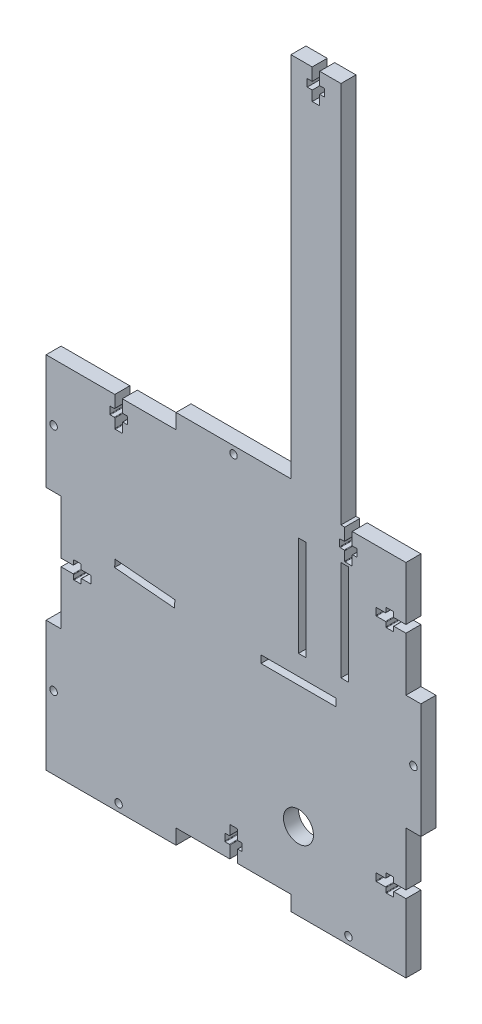
SolidWorks part; units mm, degrees
ref_plane "Front Plane" through (0, 0, 0) normal (0, 0, 1) x (1, 0, 0)
ref_plane "Top Plane" through (0, 0, 0) normal (0, 1, 0) x (1, 0, 0)
ref_plane "Right Plane" through (0, 0, 0) normal (1, 0, 0) x (0, 0, -1)
sketch "Sketch1" plane through (0, 0, 0) normal (0, 0, 1) x (1, 0, 0)
  line L0 (-69, 69) -> (-23, 69)
  line L5 (-75, -75) -> (75, -75) construction
  line L6 (-75, -75) -> (-75, 75) construction
  line L7 (-75, 75) -> (75, 75) construction
  line L8 (75, -75) -> (75, 75) construction
  line L9 (75, 23) -> (69, 23)
  line L10 (69, -23) -> (75, -23)
  line L11 (-69, -69) -> (69, -69) construction
  line L12 (-69, -69) -> (-69, 69) construction
  line L13 (-69, 69) -> (69, 69) construction
  line L14 (69, -69) -> (69, 69) construction
  line L15 (-69, -69) -> (69, 69) construction
  line L16 (69, -69) -> (69, -23)
  line L17 (-23, 69) -> (-23, 75)
  line L18 (-23, 75) -> (23, 75)
  line L19 (23, 75) -> (23, 69)
  line L20 (23, 69) -> (69, 69)
  line L21 (75, -23) -> (75, 23)
  line L22 (69, 23) -> (69, 69)
  line L23 (-75, 23) -> (-69, 23)
  line L24 (-69, 69) -> (-75, 69)
  line L25 (-75, 69) -> (-75, 23)
  line L26 (69, -69) -> (69, -75)
  line L27 (69, -75) -> (23, -75)
  line L28 (23, -75) -> (23, -69)
  line L29 (23, -69) -> (-23, -69)
  line L30 (-23, -69) -> (-23, -75)
  line L31 (-23, -75) -> (-69, -75)
  line L32 (-69, -75) -> (-69, -69) construction
  line L33 (-69, 23) -> (-69, -23)
  line L34 (-69, -23) -> (-75, -23)
  line L35 (-75, -23) -> (-75, -69)
  line L36 (-75, -69) -> (-69, -69) construction
  line L37 (-46, 69) -> (-46, -75) construction
  line L38 (-69, 69) -> (69, -69) construction
  line L39 (-75, -75) -> (-69, -75)
  line L40 (-75, -75) -> (-75, -69)
  point P0 (0, 0)
  point P6 (-7, -7)
  point P26 (0, -75)
  point P27 (-75, 0)
  dimension "D1" = 150
  dimension "D2" = 150
  dimension "D5" = 46
  dimension "D3" = 6
  dimension "D6" = 6
  dimension "D7" = 6
extrude "Box Side" add sketch "Sketch1" along normal blind 6
sketch "Sketch2" plane through (0, 0, 6) normal (0, 0, 1) x (1, 0, 0)
  line L0 (23, 72) -> (-23, 72) construction
  line L1 (23, 75) -> (23, 69) construction
  line L2 (-23, 69) -> (-23, 75) construction
  line L3 (-46, 69) -> (-46, -75) construction
  line L5 (0, 75) -> (0, 69) construction
  line L6 (-23, 75) -> (23, 75) construction
  line L7 (-69, 69) -> (69, 69) construction
  line L16 (-46, 69) -> (-46, -75) construction
  line L21 (0, -69) -> (0, 69) construction
  line L35 (-69, 69) -> (-23, 69) construction
  line L36 (-44.5, 69) -> (-44.5, 64.2)
  line L37 (-44.3, 64) -> (-42.7, 64)
  line L38 (-42.5, 63.8) -> (-42.5, 61.2)
  line L39 (-42.7, 61) -> (-44.3, 61)
  line L40 (-44.5, 60.8) -> (-44.5, 57.2)
  line L46 (-44.7, 57) -> (-47.3, 57)
  line L48 (-44.5, 69) -> (-47.5, 69)
  line L51 (-47.5, 60.8) -> (-47.5, 57.2)
  line L52 (-49.3, 61) -> (-47.7, 61)
  line L53 (-49.5, 63.8) -> (-49.5, 61.2)
  line L54 (-47.7, 64) -> (-49.3, 64)
  line L55 (-47.5, 69) -> (-47.5, 64.2)
  line L56 (47.5, 69) -> (47.5, 64.2)
  line L57 (47.7, 64) -> (49.3, 64)
  line L58 (49.5, 63.8) -> (49.5, 61.2)
  line L59 (49.3, 61) -> (47.7, 61)
  line L60 (47.5, 60.8) -> (47.5, 57.2)
  line L61 (44.5, 69) -> (47.5, 69)
  line L62 (44.7, 57) -> (47.3, 57)
  line L63 (44.5, 60.8) -> (44.5, 57.2)
  line L64 (42.7, 61) -> (44.3, 61)
  line L65 (42.5, 63.8) -> (42.5, 61.2)
  line L66 (44.3, 64) -> (42.7, 64)
  line L67 (44.5, 69) -> (44.5, 64.2)
  line L68 (-69, -69) -> (69, 69) construction
  line L69 (-69, -69) -> (69, 69) construction
  line L70 (75, 0) -> (69, 0) construction
  line L71 (72, 23) -> (72, -23) construction
  line L72 (69, 44.5) -> (64.2, 44.5)
  line L73 (64, 44.3) -> (64, 42.7)
  line L74 (63.8, 42.5) -> (61.2, 42.5)
  line L75 (61, 42.7) -> (61, 44.3)
  line L76 (60.8, 44.5) -> (57.2, 44.5)
  line L77 (57, 44.7) -> (57, 47.3)
  line L78 (69, 44.5) -> (69, 47.5)
  line L79 (60.8, 47.5) -> (57.2, 47.5)
  line L80 (61, 49.3) -> (61, 47.7)
  line L81 (63.8, 49.5) -> (61.2, 49.5)
  line L82 (64, 47.7) -> (64, 49.3)
  line L83 (69, 47.5) -> (64.2, 47.5)
  line L84 (69, -47.5) -> (64.2, -47.5)
  line L85 (64, -47.7) -> (64, -49.3)
  line L86 (63.8, -49.5) -> (61.2, -49.5)
  line L87 (61, -49.3) -> (61, -47.7)
  line L88 (60.8, -47.5) -> (57.2, -47.5)
  line L89 (69, -44.5) -> (69, -47.5)
  line L90 (57, -44.7) -> (57, -47.3)
  line L91 (60.8, -44.5) -> (57.2, -44.5)
  line L92 (61, -42.7) -> (61, -44.3)
  line L93 (63.8, -42.5) -> (61.2, -42.5)
  line L94 (64, -44.3) -> (64, -42.7)
  line L95 (69, -44.5) -> (64.2, -44.5)
  line L120 (-69, 69) -> (69, -69) construction
  line L121 (-69, 69) -> (69, -69) construction
  line L122 (-1.5, -69) -> (1.5, -69)
  line L123 (-23, -69) -> (23, -69) construction
  line L124 (1.5, -69) -> (1.5, -64.2)
  line L125 (1.7, -64) -> (3.3, -64)
  line L126 (3.5, -63.8) -> (3.5, -61.2)
  line L127 (3.3, -61) -> (1.7, -61)
  line L128 (1.5, -60.8) -> (1.5, -57.2)
  line L129 (1.3, -57) -> (-1.3, -57)
  line L130 (-1.5, -60.8) -> (-1.5, -57.2)
  line L131 (-3.3, -61) -> (-1.7, -61)
  line L132 (-3.5, -63.8) -> (-3.5, -61.2)
  line L133 (-1.7, -64) -> (-3.3, -64)
  line L134 (-1.5, -69) -> (-1.5, -64.2)
  line L135 (-69, -1.5) -> (-64.2, -1.5)
  line L136 (-64, -1.7) -> (-64, -3.3)
  line L137 (-63.8, -3.5) -> (-61.2, -3.5)
  line L138 (-61, -3.3) -> (-61, -1.7)
  line L139 (-60.8, -1.5) -> (-57.2, -1.5)
  line L140 (-57, 1.3) -> (-57, -1.3)
  line L141 (-60.8, 1.5) -> (-57.2, 1.5)
  line L142 (-61, 3.3) -> (-61, 1.7)
  line L143 (-63.8, 3.5) -> (-61.2, 3.5)
  line L144 (-64, 1.7) -> (-64, 3.3)
  line L145 (-69, 1.5) -> (-64.2, 1.5)
  line L146 (-69, -1.5) -> (-69, 1.5)
  line L147 (-69, -72) -> (-23, -72) construction
  line L148 (-23, 69) -> (-75, 69) construction
  line L149 (-23, -75) -> (-23, -69) construction
  line L150 (-69, -69) -> (-69, -75) construction
  line L151 (-75, -75) -> (-23, -75) construction
  circle A0 centre (0, 72) radius 1.5
  arc A1 (-44.5, 57.2) -> (-44.7, 57) centre (-44.7, 57.2) cw
  arc A2 (-44.3, 61) -> (-44.5, 60.8) centre (-44.3, 60.8) ccw
  arc A3 (-42.5, 61.2) -> (-42.7, 61) centre (-42.7, 61.2) cw
  arc A4 (-42.7, 64) -> (-42.5, 63.8) centre (-42.7, 63.8) cw
  arc A5 (-44.5, 64.2) -> (-44.3, 64) centre (-44.3, 64.2) ccw
  arc A6 (-47.5, 64.2) -> (-47.7, 64) centre (-47.7, 64.2) cw
  arc A7 (-49.3, 64) -> (-49.5, 63.8) centre (-49.3, 63.8) ccw
  arc A8 (-49.5, 61.2) -> (-49.3, 61) centre (-49.3, 61.2) ccw
  arc A9 (-47.7, 61) -> (-47.5, 60.8) centre (-47.7, 60.8) cw
  arc A10 (-47.5, 57.2) -> (-47.3, 57) centre (-47.3, 57.2) ccw
  arc A11 (47.5, 57.2) -> (47.3, 57) centre (47.3, 57.2) cw
  arc A12 (47.7, 61) -> (47.5, 60.8) centre (47.7, 60.8) ccw
  arc A13 (49.5, 61.2) -> (49.3, 61) centre (49.3, 61.2) cw
  arc A14 (49.3, 64) -> (49.5, 63.8) centre (49.3, 63.8) cw
  arc A15 (47.5, 64.2) -> (47.7, 64) centre (47.7, 64.2) ccw
  arc A16 (44.5, 64.2) -> (44.3, 64) centre (44.3, 64.2) cw
  arc A17 (42.7, 64) -> (42.5, 63.8) centre (42.7, 63.8) ccw
  arc A18 (42.5, 61.2) -> (42.7, 61) centre (42.7, 61.2) ccw
  arc A19 (44.3, 61) -> (44.5, 60.8) centre (44.3, 60.8) cw
  arc A20 (44.5, 57.2) -> (44.7, 57) centre (44.7, 57.2) ccw
  arc A21 (57.2, 44.5) -> (57, 44.7) centre (57.2, 44.7) cw
  arc A22 (61, 44.3) -> (60.8, 44.5) centre (60.8, 44.3) ccw
  arc A23 (61.2, 42.5) -> (61, 42.7) centre (61.2, 42.7) cw
  arc A24 (64, 42.7) -> (63.8, 42.5) centre (63.8, 42.7) cw
  arc A25 (64.2, 44.5) -> (64, 44.3) centre (64.2, 44.3) ccw
  arc A26 (64.2, 47.5) -> (64, 47.7) centre (64.2, 47.7) cw
  arc A27 (64, 49.3) -> (63.8, 49.5) centre (63.8, 49.3) ccw
  arc A28 (61.2, 49.5) -> (61, 49.3) centre (61.2, 49.3) ccw
  arc A29 (61, 47.7) -> (60.8, 47.5) centre (60.8, 47.7) cw
  arc A30 (57.2, 47.5) -> (57, 47.3) centre (57.2, 47.3) ccw
  arc A31 (57.2, -47.5) -> (57, -47.3) centre (57.2, -47.3) cw
  arc A32 (61, -47.7) -> (60.8, -47.5) centre (60.8, -47.7) ccw
  arc A33 (61.2, -49.5) -> (61, -49.3) centre (61.2, -49.3) cw
  arc A34 (64, -49.3) -> (63.8, -49.5) centre (63.8, -49.3) cw
  arc A35 (64.2, -47.5) -> (64, -47.7) centre (64.2, -47.7) ccw
  arc A36 (64.2, -44.5) -> (64, -44.3) centre (64.2, -44.3) cw
  arc A37 (64, -42.7) -> (63.8, -42.5) centre (63.8, -42.7) ccw
  arc A38 (61.2, -42.5) -> (61, -42.7) centre (61.2, -42.7) ccw
  arc A39 (61, -44.3) -> (60.8, -44.5) centre (60.8, -44.3) cw
  arc A40 (57.2, -44.5) -> (57, -44.7) centre (57.2, -44.7) ccw
  circle A41 centre (72, 0) radius 1.5
  arc A62 (1.5, -57.2) -> (1.3, -57) centre (1.3, -57.2) ccw
  arc A63 (1.7, -61) -> (1.5, -60.8) centre (1.7, -60.8) cw
  arc A64 (3.5, -61.2) -> (3.3, -61) centre (3.3, -61.2) ccw
  arc A65 (3.3, -64) -> (3.5, -63.8) centre (3.3, -63.8) ccw
  arc A66 (1.5, -64.2) -> (1.7, -64) centre (1.7, -64.2) cw
  arc A67 (-1.5, -64.2) -> (-1.7, -64) centre (-1.7, -64.2) ccw
  arc A68 (-3.3, -64) -> (-3.5, -63.8) centre (-3.3, -63.8) cw
  arc A69 (-3.5, -61.2) -> (-3.3, -61) centre (-3.3, -61.2) cw
  arc A70 (-1.7, -61) -> (-1.5, -60.8) centre (-1.7, -60.8) ccw
  arc A71 (-1.5, -57.2) -> (-1.3, -57) centre (-1.3, -57.2) cw
  arc A72 (-57.2, -1.5) -> (-57, -1.3) centre (-57.2, -1.3) ccw
  arc A73 (-61, -1.7) -> (-60.8, -1.5) centre (-60.8, -1.7) cw
  arc A74 (-61.2, -3.5) -> (-61, -3.3) centre (-61.2, -3.3) ccw
  arc A75 (-64, -3.3) -> (-63.8, -3.5) centre (-63.8, -3.3) ccw
  arc A76 (-64.2, -1.5) -> (-64, -1.7) centre (-64.2, -1.7) cw
  arc A77 (-64.2, 1.5) -> (-64, 1.7) centre (-64.2, 1.7) ccw
  arc A78 (-64, 3.3) -> (-63.8, 3.5) centre (-63.8, 3.3) cw
  arc A79 (-61.2, 3.5) -> (-61, 3.3) centre (-61.2, 3.3) cw
  arc A80 (-61, 1.7) -> (-60.8, 1.5) centre (-60.8, 1.7) ccw
  arc A81 (-57.2, 1.5) -> (-57, 1.3) centre (-57.2, 1.3) cw
  circle A82 centre (-46, -72) radius 1.5
  circle A83 centre (46, -72) radius 1.5
  circle A84 centre (-72, 46) radius 1.5
  circle A85 centre (-72, -46) radius 1.5
  point P6 (0, 72)
  point P38 (0, 0)
  point P56 (-46, 57)
  point P88 (46, 57)
  point P161 (57, 46)
  point P162 (57, -46)
  point P198 (0, -57)
  point P231 (-57, 0)
  point P234 (-42.5, 62.5)
  dimension "D1" = 3
  dimension "D2" = 0.2
  dimension "D8" = 0.2
  dimension "D14" = 3
  dimension "D4" = 3
  dimension "D7" = 1.5
  dimension "D10" = 3
  dimension "D12" = 1.5
  dimension "D9" = 12
  dimension "D11" = 5
  dimension "D13" = 7
  dimension "D3" = 12
  dimension "D5" = 7
  dimension "D6" = 5
extrude "Screw Cut-outs" cut sketch "Sketch2" against normal through all
sketch "Bearing Hole" plane through (0, 0, 6) normal (0, 0, 1) x (1, 0, 0)
  line L0 (20, -69) -> (50020, -69) construction
  line L1 (69, -44.5) -> (69, -23) construction
  line L4 (26, -41) -> (50026, -41) construction
  line L5 (26.5774, -47) -> (50026.5774, -47) construction
  line L8 (29, -52) -> (29, -50052) construction
  circle A0 centre (26, -44) radius 3 construction
  circle A1 centre (26, -54) radius 15 construction
  circle A2 centre (26, -44) radius 6
  dimension "D2" = 6
  dimension "D4" = 30
  dimension "D5" = 12
  dimension "D1" = 7
  dimension "D3" = 43
extrude "Shaft Hole" cut sketch "Bearing Hole" against normal through all
sketch "Sketch4" plane through (0, 0, 0) normal (0, 0, -1) x (-1, 0, 0)
  line L0 (-72, 1.5) -> (49928, 1.5) construction
  line L1 (-41, 8) -> (-11, 8)
  line L2 (-41, 8) -> (-41, 5)
  line L3 (-41, 5) -> (-11, 5)
  line L4 (-11, 8) -> (-11, 5)
  line L5 (-75, -23) -> (-75, 23) construction
  line L6 (-69, 23) -> (-69, 44.5) construction
  line L7 (-46, 56) -> (-43, 56)
  line L8 (-46, 56) -> (-46, 16)
  line L9 (-46, 16) -> (-43, 16)
  line L10 (-43, 56) -> (-43, 16)
  line L11 (-29, 56) -> (-26, 56)
  line L12 (-29, 56) -> (-29, 16)
  line L13 (-29, 16) -> (-26, 16)
  line L14 (-26, 56) -> (-26, 16)
  line L15 (-44.5, 69) -> (-23, 69) construction
  circle A1 centre (-72, 0) radius 1.5 construction
  point P18 (-29, 36)
  dimension "D1" = 3.5
  dimension "D2" = 30
  dimension "D3" = 3
  dimension "D4" = 34
  dimension "D5" = 14
  dimension "D6" = 23
  dimension "D7" = 13
  dimension "D8" = 3
  dimension "D9" = 40
extrude "Grooves" cut sketch "Sketch4" against normal up to surface (6 mm away) up to face at (32, -44, 6)
sketch "Sketch5" plane through (0, 69, 0) normal (0, 1, 0) x (1, 0, 0)
  line L0 (69, 0) -> (47.5, 0) construction
  line L1 (23, -6) -> (43, -6)
  line L2 (23, -6) -> (23, 0)
  line L3 (23, 0) -> (43, 0)
  line L4 (43, -6) -> (43, 0)
  line L5 (75, -6) -> (75, 0) construction
  dimension "D1" = 32
extrude "Boss-Extrude1" add sketch "Sketch5" along normal blind 153
sketch "Sketch6" plane through (0, 0, 0) normal (0, 0, -1) x (-1, 0, 0)
  line L0 (-34.5, 222) -> (-34.5, 217)
  line L1 (-43, 222) -> (-23, 222) construction
  line L2 (-34.5, 217) -> (-36.5, 217)
  line L3 (-36.5, 217) -> (-36.5, 214)
  line L4 (-36.5, 214) -> (-34.5, 214)
  line L5 (-34.5, 214) -> (-34.5, 210)
  line L6 (-34.5, 210) -> (-31.5, 210)
  line L7 (-31.5, 210) -> (-31.5, 214)
  line L8 (-31.5, 214) -> (-29.5, 214)
  line L9 (-29.5, 214) -> (-29.5, 217)
  line L10 (-29.5, 217) -> (-31.5, 217)
  line L11 (-31.5, 217) -> (-31.5, 222)
  line L12 (-34.5, 222) -> (-31.5, 222)
  line L13 (-29.5, 214) -> (-36.5, 214)
  point P4 (-33, 210)
  point P16 (-33, 222)
  point P17 (-33, 214)
  point P18 (-33, 222)
  dimension "D1" = 3
  dimension "D2" = 7
  dimension "D3" = 5
  dimension "D4" = 12
  dimension "D5" = 3
extrude "Cut-Extrude1" cut sketch "Sketch6" against normal through all contours L13 L8 L9 L10 L11 L12 L0 L2 L3 L4 | L7 L13 L5 L6 region at (33, 217.1667, 0) region at (33, 212, 0)
sketch "Sketch7" plane through (0, 0, 0) normal (0, 0, -1) x (-1, 0, 0)
  line L4 (2, 40.5315) -> (2, -49959.4685) construction
  line L6 (69, 23) -> (69, 1.5) construction
  line L8 (22.5921, 19.3161) -> (4380.3792, -49790.4188) construction
  line L9 (2, 8) -> (23.4182, 9.8738) construction
  line L10 (23.4182, 9.8738) -> (23.6797, 6.8853)
  line L11 (23.6797, 6.8853) -> (47.5883, 8.977)
  line L12 (47.5883, 8.977) -> (47.3269, 11.9656)
  line L13 (47.3269, 11.9656) -> (23.4182, 9.8738)
  line L14 (23, 69) -> (44.5, 69) construction
  dimension "D1" = 67
  dimension "D2" = 5
  dimension "D3" = 21.5
  dimension "D4" = 24
  dimension "D5" = 3
  dimension "D6" = 61
extrude "Cut-Extrude2" cut sketch "Sketch7" against normal through all
equation "\"filletRadius\"=0.2"
equation "\"D8@Sketch2\"=\"filletRadius\""
equation "\"D2@Sketch2\"=\"filletRadius\""
equation "\"fingerWidth\"= 46"
equation "\"D5@Sketch1\"=\"fingerWidth\""
equation "\"wallThickness\"= 6"
equation "\"D3@Sketch1\" = \"wallThickness\""
equation "\"D6@Sketch1\" = \"wallThickness\""
equation "\"D7@Sketch1\" = \"wallThickness\""
equation "\"D1@Box Side\" = \"wallThickness\""
equation "\"M3\"= 3"
equation "\"D14@Sketch2\"=\"M3\""
equation "\"D1@Sketch2\"=\"M3\""
equation "\"D12@Sketch2\"=\"M3\"/2"
equation "\"nutThickness\"=3"
equation "\"D10@Sketch2\" = \"nutThickness\""
equation "\"boltLength\"= 12"
equation "\"D9@Sketch2\" = \"boltLength\""
equation "\"distanceToNut\"= 5"
equation "\"D11@Sketch2\" = \"distanceToNut\""
equation "\"D13@Sketch2\" = \"nutWidth\""
equation "\"D7@Sketch2\"=\"M3\"/2"
equation "\"D4@Sketch2\" = \"nutThickness\""
equation "\"D3@Sketch2\" = \"boltLength\""
equation "\"D5@Sketch2\" = \"nutWidth\""
equation "\"D6@Sketch2\" = \"distanceToNut\""
equation "\"sideLength\"=150"
equation "\"D1@Sketch1\"=\"sideLength\""
equation "\"D2@Sketch1\"=\"sideLength\""
equation "\"nutWidth\"=7"
equation "\"D1@Sketch6\"=\"M3\""
equation "\"D2@Sketch6\"=\"nutWidth\""
equation "\"D3@Sketch6\"=\"distanceToNut\""
equation "\"D4@Sketch6\"=\"boltLength\""
equation "\"D5@Sketch6\"=\"nutThickness\""
